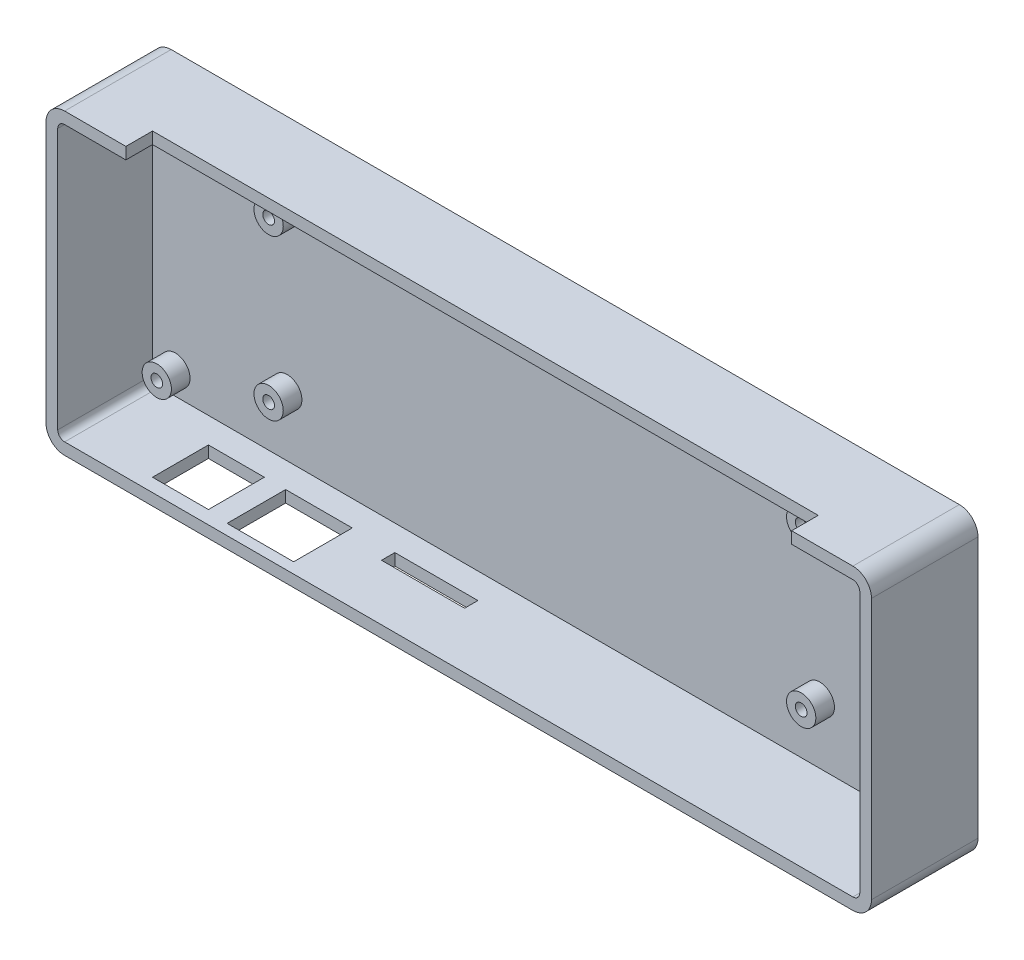
SolidWorks part; units mm, degrees
ref_plane "前视基准面" through (0, 0, 0) normal (0, 0, 1) x (1, 0, 0)
ref_plane "上视基准面" through (0, 0, 0) normal (0, 1, 0) x (1, 0, 0)
ref_plane "右视基准面" through (0, 0, 0) normal (1, 0, 0) x (0, 0, -1)
other "Configuration Table"
sketch "草图1" plane through (0, 0, 0) normal (0, 0, 1) x (1, 0, 0)
  line L1 (0, 0) -> (155, 0)
  line L2 (0, 0) -> (0, -56)
  line L3 (0, -56) -> (155, -56)
  line L4 (155, 0) -> (155, -56)
  dimension "D1" = 155
  dimension "D2" = 56
extrude "凸台-拉伸1" add sketch "草图1" along normal blind 20
fillet "圆角1" radius 3.5 4 edges at (0, 0, 10) (0, -56, 10) (155, 0, 10) (155, -56, 10)
shell "抽壳1" thickness 2.2 removed face at (77.5, -28, 20)
sketch "草图2" plane through (0, 0, 2.2) normal (0, 0, 1) x (1, 0, 0)
  line L0 (151.5, 0) -> (3.5, 0) construction
  line L1 (0, -3.5) -> (0, -52.5) construction
  circle A0 centre (27.5, -12.5) radius 1.1
  circle A2 centre (127.5, -12.5) radius 1.1
  circle A3 centre (127.5, -42.5) radius 1.1
  circle A4 centre (27.5, -42.5) radius 1.1
  dimension "D1" = 2.2
  dimension "D2" = 12.5
  dimension "D3" = 27.5
  dimension "D4" = 2
  dimension "D5" = 2
extrude "切除-拉伸1" cut sketch "草图2" against normal blind 10
sketch "草图3" plane through (0, 0, 2.2) normal (0, 0, 1) x (1, 0, 0)
  line L0 (0, -3.5) -> (0, -52.5) construction
  line L1 (151.5, 0) -> (3.5, 0) construction
  circle A0 centre (27.5, -12.5) radius 2.75
  circle A1 centre (27.5, -12.5) radius 1.1 construction
  circle A2 centre (27.5, -12.5) radius 1.1
  circle A3 centre (127.5, -12.5) radius 1.1
  circle A4 centre (127.5, -12.5) radius 2.75
  circle A5 centre (127.5, -42.5) radius 1.1
  circle A6 centre (127.5, -42.5) radius 2.75
  circle A7 centre (27.5, -42.5) radius 1.1
  circle A8 centre (27.5, -42.5) radius 2.75
  circle A9 centre (6.5, -7.5) radius 2.75
  circle A10 centre (6.5, -7.5) radius 1.1
  circle A11 centre (148.5, -7.5) radius 1.1
  circle A12 centre (148.5, -7.5) radius 2.75
  circle A13 centre (148.5, -49.5) radius 1.1
  circle A14 centre (148.5, -49.5) radius 2.75
  circle A15 centre (6.5, -49.5) radius 1.1
  circle A16 centre (6.5, -49.5) radius 2.75
  dimension "D1" = 5.5
  dimension "D4" = 5.5
  dimension "D7" = 2.2
  dimension "D5" = 6.5
  dimension "D6" = 7.5
  dimension "D2" = 2
  dimension "D3" = 2
  dimension "D8" = 2
  dimension "D9" = 2
extrude "凸台-拉伸2" add sketch "草图3" along normal blind 3.5
sketch "草图4" plane through (0, -56, 0) normal (0, -1, 0) x (1, 0, 0)
  line L1 (17.5, 17.5) -> (28, 17.5)
  line L2 (17.5, 17.5) -> (17.5, 7)
  line L3 (17.5, 7) -> (28, 7)
  line L4 (28, 17.5) -> (28, 7)
  line L5 (3.5, 0) -> (151.5, 0) construction
  line L6 (32, 18) -> (44.5, 18)
  line L7 (32, 18) -> (32, 7)
  line L8 (32, 7) -> (44.5, 7)
  line L9 (44.5, 18) -> (44.5, 7)
  line L10 (52.5, 9.5) -> (68.1, 9.5)
  line L11 (52.5, 9.5) -> (52.5, 7)
  line L12 (52.5, 7) -> (68.1, 7)
  line L13 (68.1, 9.5) -> (68.1, 7)
  line L14 (0, 0) -> (0, 20) construction
  dimension "D1" = 2.5
  dimension "D2" = 15.6
  dimension "D3" = 11
  dimension "D4" = 12.5
  dimension "D5" = 10.5
  dimension "D6" = 10.5
  dimension "D7" = 7
  dimension "D8" = 17.5
  dimension "D9" = 4
  dimension "D10" = 8
extrude "切除-拉伸2" cut sketch "草图4" against normal blind 3
sketch "草图5" plane through (0, 0, 0) normal (0, 1, 0) x (1, 0, 0)
  line L0 (151.5, -20) -> (3.5, -20) construction
  line L1 (15, -20) -> (140, -20)
  line L2 (15, -20) -> (15, -15)
  line L3 (15, -15) -> (140, -15)
  line L12 (140, -20) -> (140, -15)
  line L13 (155, 0) -> (155, -20) construction
  line L14 (0, -20) -> (0, 0) construction
  dimension "D1" = 5
  dimension "D2" = 15
  dimension "D3" = 15
extrude "切除-拉伸3" cut sketch "草图5" against normal blind 3
